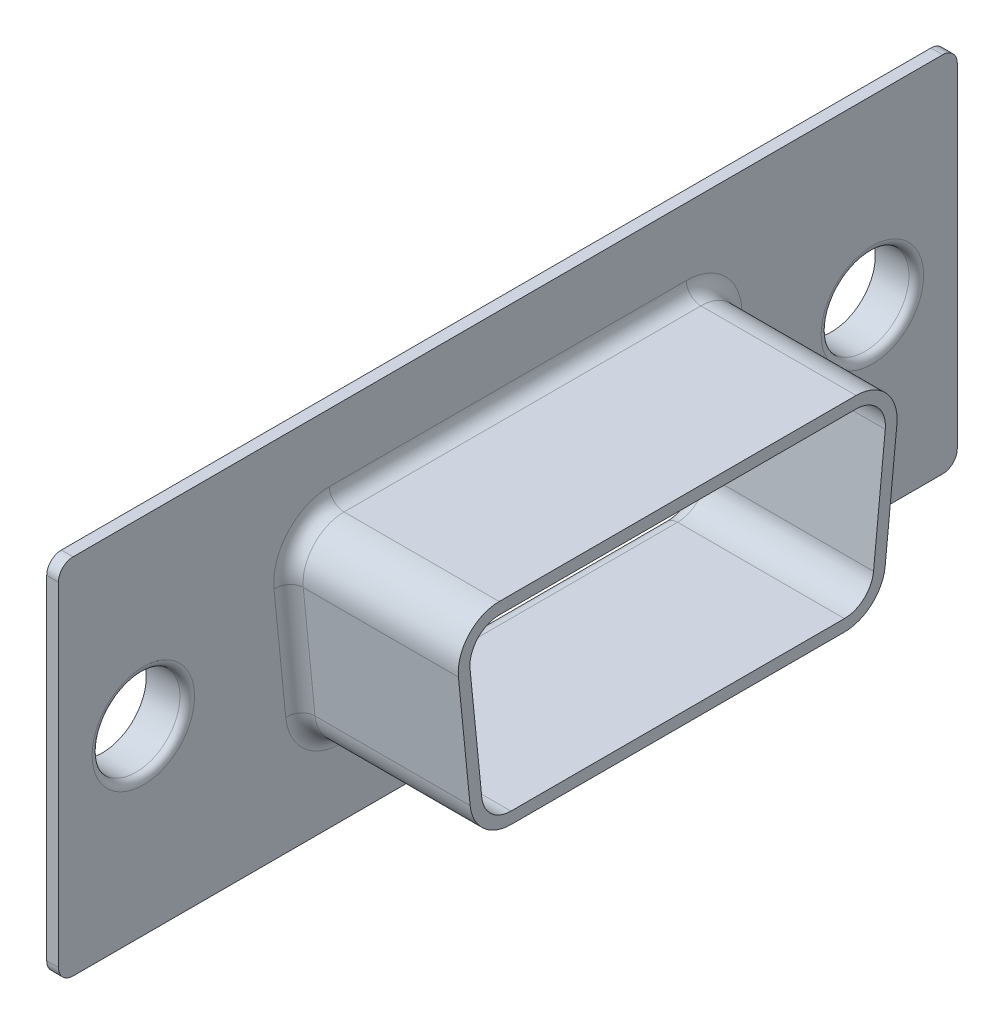
SolidWorks part; units mm, degrees
ref_plane "前视基准面" through (0, 0, 0) normal (0, 0, 1) x (1, 0, 0)
ref_plane "上视基准面" through (0, 0, 0) normal (0, 1, 0) x (1, 0, 0)
ref_plane "右视基准面" through (0, 0, 0) normal (1, 0, 0) x (0, 0, -1)
sketch "草图1" plane through (0, 0, 0) normal (1, 0, 0) x (0, 0, -1)
  line L0 (0, -1000) -> (0, 49000) construction
  line L1 (-1000, 0) -> (49000, 0) construction
  line L4 (-6.095, 3) -> (6.095, 3)
  line L5 (7.09, 1.9005) -> (6.69, -2.0995)
  line L6 (-6.095, 3.4) -> (6.095, 3.4)
  line L7 (-5.695, -3) -> (5.695, -3)
  line L8 (-7.09, 1.9005) -> (-6.69, -2.0995)
  line L9 (7.4881, 1.8607) -> (7.0881, -2.1393)
  line L10 (-5.695, -3.4) -> (5.695, -3.4)
  line L11 (-7.4881, 1.8607) -> (-7.0881, -2.1393)
  arc A0 (6.69, -2.0995) -> (5.695, -3) centre (5.695, -2) cw
  arc A1 (-5.695, -3) -> (-6.69, -2.0995) centre (-5.695, -2) cw
  arc A2 (7.09, 1.9005) -> (6.095, 3) centre (6.095, 2) ccw
  arc A3 (-6.095, 3) -> (-7.09, 1.9005) centre (-6.095, 2) ccw
  arc A4 (7.4881, 1.8607) -> (6.095, 3.4) centre (6.095, 2) ccw
  arc A5 (7.0881, -2.1393) -> (5.695, -3.4) centre (5.695, -2) cw
  arc A6 (-5.695, -3.4) -> (-7.0881, -2.1393) centre (-5.695, -2) cw
  arc A7 (-6.095, 3.4) -> (-7.4881, 1.8607) centre (-6.095, 2) ccw
  point P9 (6.6, -3)
  point P15 (-6.6, -3)
  point P18 (7.2, 3)
  point P21 (-7.2, 3)
  dimension "D4" = 1
  dimension "D1" = 6
  dimension "D2" = 14.4
  dimension "D3" = 13.2
  dimension "D6" = 6
  dimension "D5" = 0.4
sheet metal parameters "钣金2" thickness 5.8 parameters "D1"=0.7366, "厚度"=5.8
base flange "基体-法兰2" sketch "草图1" thickness 5.8 reverse thickness direction no parameters "D1"=0.7366
sketch "草图10" plane through (-5.8, 0, 0) normal (-1, 0, 0) x (0, 0, 1)
  line L0 (0, -1000) -> (0, 49000) construction
  line L1 (-1000, 0) -> (49000, 0) construction
  line L2 (-15.35, 6.2) -> (15.35, 6.2)
  line L3 (-15.35, 6.2) -> (-15.35, -6.2)
  line L4 (15.35, 6.2) -> (15.35, -6.2)
  line L5 (-15.35, -6.2) -> (15.35, -6.2)
  line L6 (0, 3.4) -> (0, 6.2)
  line L7 (-6.095, 3.4) -> (6.095, 3.4) construction
  point P10 (0, 6.2)
  dimension "D2" = 12.4
extrude "凸台-拉伸1" add sketch "草图10" along normal blind 0.4 contours L2 L4 L5 L3
sketch "草图11" plane through (-5.8, 0, 0) normal (1, 0, 0) x (0, 0, -1)
  line L2 (-7.0853, 1.9017) -> (-6.6902, -2.0983)
  line L5 (-5.695, -3) -> (5.695, -3)
  line L8 (6.69, -2.0995) -> (7.09, 1.9005)
  line L11 (6.095, 3) -> (-6.0901, 3)
  arc A6 (-7.0853, 1.9017) -> (-6.0901, 3) centre (-6.0901, 2) cw
  arc A7 (7.09, 1.9005) -> (6.095, 3) centre (6.095, 2) ccw
  arc A8 (5.695, -3) -> (6.69, -2.0995) centre (5.695, -2) ccw
  arc A9 (-5.695, -3) -> (-6.6902, -2.0983) centre (-5.695, -2) cw
  dimension "D1" = 1
  dimension "D2" = 1
  dimension "D3" = 1
  dimension "D4" = 1
extrude "切除-拉伸1" cut sketch "草图11" against normal through all normal cut yes
fillet "圆角1" radius 0.5 16 edges at (-6.2, -2.7415, -6.366) (-6.2, -3, 0) (-6.2, -2.741, 6.3665) (-6.2, -0.0983, 6.8877) (-6.2, 2.6715, 6.8312) (-6.2, 3, -0.0024) (-6.2, 2.671, -6.8365) (-5.8, -3.038, -6.6344) (-5.8, -3.4, 0) (-5.8, -3.038, 6.6344) (-5.8, -0.1393, 7.2881) (-5.8, 2.9394, 7.133) (-5.8, 3.4, 0) (-5.8, 2.9394, -7.133) (-6.2, -0.0995, -6.89) (-5.8, -0.1393, -7.2881)
sketch "草图13" plane through (-5.8, 0, 0) normal (1, 0, 0) x (0, 0, -1)
  line L0 (15.35, 6.2) -> (15.35, -6.2) construction
  line L1 (0, -1000) -> (0, 49000) construction
  circle A0 centre (12.45, 0) radius 1.5
  circle A1 centre (-12.45, 0) radius 1.5
  dimension "D1" = 3
  dimension "D2" = 2.9
extrude "切除-拉伸2" cut sketch "草图13" against normal through all normal cut yes
fillet "圆角2" radius 0.5 4 edges at (-6, -6.2, -15.35) (-6, 6.2, -15.35) (-6, 6.2, 15.35) (-6, -6.2, 15.35)
sketch "草图15" plane through (-6.2, 0, 0) normal (-1, 0, 0) x (0, 0, 1)
  circle A0 centre (-12.45, 0) radius 1.5
  circle A1 centre (-12.45, 0) radius 1.6
  dimension "D1" = 3.2
  dimension "D2" = 3
extrude "凸台-拉伸2" add sketch "草图15" along normal blind 1
fillet "圆角3" radius 0.25 2 edges at (-5.8, 0, -13.95) (-6.2, 0, -10.85)
mirror "镜向1" about plane through (0, 0, 0) normal (0, 0, 1) of "凸台-拉伸2"
fillet "圆角4" radius 0.25 2 edges at (-5.8, 0, 13.95) (-6.2, 0, 14.05)
flat pattern "平板型式2" [suppressed]
sketch "折弯-线2" plane through (0, 0, 0) normal (0, 1, 0) x (-1, 0, 0)
sketch "边界框2" [suppressed] plane through (0, 0, 0) normal (0, 1, 0) x (-1, 0, 0)
